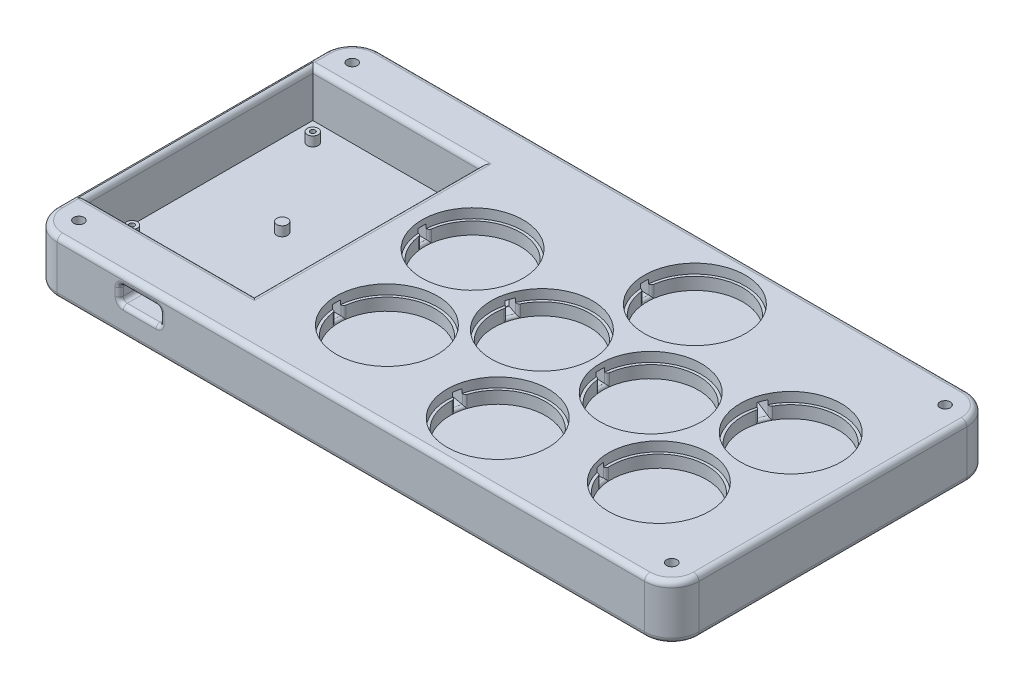
SolidWorks part; units mm, degrees
note: The reader was unsure of these and kept them because the rebuilt part matched: shared geometry of "Sketch1<3>", "Sketch1<5>", "Sketch1<6>".
ref_plane "Front Plane" through (0, 0, 0) normal (0, 0, 1) x (1, 0, 0)
ref_plane "Top Plane" through (0, 0, 0) normal (0, 1, 0) x (1, 0, 0)
ref_plane "Right Plane" through (0, 0, 0) normal (1, 0, 0) x (0, 0, -1)
sketch "Sketch1" plane through (0, 0, 0) normal (0, 1, 0) x (1, 0, 0)
  line L0 (-50.1645, 82.8261) -> (10.8355, 82.8261) construction
  line L1 (-50.1645, 0.3261) -> (10.8355, 0.3261) construction
  line L2 (-50.1645, 0.3261) -> (-50.1645, 82.8261) construction
  line L3 (-50.1645, 82.8261) -> (10.8355, 82.8261) construction
  line L4 (10.8355, 0.3261) -> (10.8355, 82.8261) construction
  line L6 (-50.1645, 82.8261) -> (-50.1645, 0.3261) construction
  line L9 (95.3355, 77.8261) -> (95.3355, 5.3261) construction
  line L10 (95.3355, 41.5761) -> (-73.6645, 41.5761) construction
  line L11 (-53.6645, 100.8261) -> (182.3355, 100.8261)
  line L12 (-50.6645, 97.8261) -> (179.3355, 97.8261)
  line L13 (-50.6645, 97.8261) -> (-50.6645, -14.6739)
  line L14 (-50.6645, -14.6739) -> (179.3355, -14.6739)
  line L15 (179.3355, 97.8261) -> (179.3355, -14.6739)
  line L16 (182.3355, 100.8261) -> (182.3355, -17.6739)
  line L17 (-53.6645, -17.6739) -> (182.3355, -17.6739)
  line L18 (-53.6645, 100.8261) -> (-53.6645, -17.6739)
  line L19 (-50.4645, 83.1261) -> (11.1355, 83.1261)
  line L20 (11.1355, 0.0261) -> (11.1355, 83.1261)
  line L21 (-50.4645, 0.0261) -> (11.1355, 0.0261)
  line L22 (-50.4645, 83.1261) -> (-50.4645, 0.0261)
  circle A0 centre (36.8355, 54.5761) radius 17.6
  circle A1 centre (45.3355, 14.5761) radius 17.6
  circle A2 centre (145.3355, 14.5761) radius 17.6
  circle A4 centre (75.3355, 41.5761) radius 17.6
  circle A5 centre (115.3355, 41.5761) radius 17.6
  circle A6 centre (95.3355, 5.3261) radius 17.6
  circle A7 centre (153.8355, 54.5761) radius 17.6
  circle A8 centre (95.3355, 77.8261) radius 17.6
  point P12 (10.8355, 41.5761)
  point P27 (-50.6645, 41.5761)
  dimension "D3" = 35.2
  dimension "D4" = 26
  dimension "D5" = 40
  dimension "D15" = 112.5
  dimension "D20" = 82.5
  dimension "D1" = 61
  dimension "D2" = 82.5
  dimension "D6" = 20
  dimension "D7" = 72.5
  dimension "D8" = 36.25
  dimension "D9" = 100
  dimension "D10" = 30
  dimension "D11" = 117
  dimension "D12" = 38.5
  dimension "D13" = 40
  dimension "D14" = 27
  dimension "D16" = 230
  dimension "D17" = 3
  dimension "D18" = 0.5
  dimension "D19" = 0.3
extrude "Boss-Extrude1" add sketch "Sketch1" against normal blind 5 contours L15 L12 L13 L14 A8 A7 A6 A5 A4 A2 A1 A0 L6 L0 L4 L1 | L11 L18 L17 L16 L12 L15 L14 L13 | L0 L6 L1 L4 | A0 | A1 | A4 | A8 | A5 | A7 | A2 | A6 | L19 L22 L21 L20
extrude "Boss-Extrude2" add sketch "Sketch1<3>" along normal blind 15 contours L11 L18 L17 L16 L12 L15 L14 L13 | L15 L12 L13 L14 A8 A7 A6 A5 A4 A2 A1 A0 L22 L19 L20 L21
sketch "Sketch1<3>" plane through (0, 0, 0) normal (0, 1, 0) x (1, 0, 0) same geometry as "Sketch1"
extrude "Cut-Extrude2" cut sketch "Sketch1<5>" against normal blind 2 contours L0 L6 L1 L4 | A0 | A1 | A4 | A8 | A5 | A7 | A2 | A6 | L19 L22 L21 L20
sketch "Sketch1<5>" plane through (0, 0, 0) normal (0, 1, 0) x (1, 0, 0) same geometry as "Sketch1"
ref_plane "Plane1" through (0, 12, 0) normal (0, 1, 0) x (1, 0, 0)
sketch "Sketch2" plane through (0, 12, 0) normal (0, 1, 0) x (1, 0, 0)
  line L0 (27.7355, 14.5761) -> (11.1355, 14.5761) construction
  line L1 (19.2355, 54.5761) -> (11.1355, 54.5761) construction
  line L2 (19.2995, 56.0761) -> (11.1355, 56.0761)
  line L3 (27.7995, 16.0761) -> (11.1355, 16.0761)
  line L4 (182.3355, 100.8261) -> (-53.6645, 100.8261)
  line L5 (-53.6645, 100.8261) -> (-53.6645, -17.6739)
  line L6 (-53.6645, -17.6739) -> (182.3355, -17.6739)
  line L7 (182.3355, -17.6739) -> (182.3355, 100.8261)
  line L8 (182.3355, 100.8261) -> (-53.6645, 100.8261)
  line L9 (-53.6645, 100.8261) -> (-53.6645, -17.6739)
  line L10 (-53.6645, -17.6739) -> (182.3355, -17.6739)
  line L11 (182.3355, -17.6739) -> (182.3355, 100.8261)
  line L12 (11.1355, 83.1261) -> (-50.4645, 83.1261)
  line L13 (-50.4645, 83.1261) -> (-50.4645, 0.0261)
  line L14 (-50.4645, 0.0261) -> (11.1355, 0.0261)
  line L15 (11.1355, 0.0261) -> (11.1355, 83.1261)
  line L16 (11.1355, 83.1261) -> (-50.4645, 83.1261)
  line L17 (-50.4645, 83.1261) -> (-50.4645, 0.0261)
  line L18 (-50.4645, 0.0261) -> (11.1355, 0.0261)
  line L19 (11.1355, 0.0261) -> (11.1355, 83.1261)
  line L20 (27.7995, 13.0761) -> (11.1355, 13.0761)
  line L21 (11.1355, 77.8261) -> (77.7355, 77.8261) construction
  line L22 (11.1355, 76.3261) -> (77.7995, 76.3261)
  line L23 (11.1355, 79.3261) -> (77.7995, 79.3261)
  line L24 (58.6605, 47.2066) -> (53.5105, 48.9456) construction
  line L25 (59.201, 48.6073) -> (53.9297, 50.3872)
  line L26 (58.2412, 45.765) -> (52.97, 47.5449)
  line L27 (62.6418, 11.3744) -> (78.0292, 8.5278) construction
  line L28 (62.306, 9.9111) -> (77.8193, 7.0411)
  line L29 (62.8517, 12.861) -> (78.365, 9.9911)
  line L30 (45.0626, 13.1011) -> (95.0626, 3.8511) construction
  line L31 (45.6084, 16.0511) -> (95.6084, 6.8011) construction
  line L32 (112.6418, 8.5278) -> (128.0292, 11.3744) construction
  line L33 (112.8517, 7.0411) -> (128.365, 9.9111)
  line L34 (112.306, 9.9911) -> (127.8193, 12.861)
  line L35 (95.6084, 3.8511) -> (145.6084, 13.1011) construction
  line L36 (95.0626, 6.8011) -> (145.0626, 16.0511) construction
  line L37 (95.3355, 5.3261) -> (145.3355, 14.5761) construction
  line L38 (92.9355, 41.5761) -> (97.7355, 41.5761) construction
  line L39 (92.8715, 40.0761) -> (97.7995, 40.0761)
  line L40 (92.8715, 43.0761) -> (97.7995, 43.0761)
  line L41 (111.6911, 71.3258) -> (137.4799, 61.0764) construction
  line L42 (111.0776, 69.9555) -> (136.9854, 59.6588)
  line L43 (112.1856, 72.7434) -> (138.0934, 62.4467)
  line L44 (94.7815, 76.4321) -> (153.2815, 53.1821) construction
  line L45 (95.3355, 77.8261) -> (153.8355, 54.5761) construction
  line L46 (95.8895, 79.22) -> (154.3895, 55.97) construction
  line L47 (45.3355, 14.5761) -> (95.3355, 5.3261) construction
  line L48 (27.7355, 16.0761) -> (11.1355, 16.0761) construction
  line L49 (27.7355, 13.0761) -> (11.1355, 13.0761) construction
  line L50 (19.2995, 53.0761) -> (11.1355, 53.0761)
  line L51 (25.2691, 56.0761) -> (5.5876, 56.0761) construction
  line L52 (25.2691, 54.5761) -> (5.5876, 54.5761) construction
  line L53 (25.2691, 53.0761) -> (5.5876, 53.0761) construction
  line L54 (11.1355, 79.3261) -> (77.7355, 79.3261) construction
  line L55 (11.1355, 76.3261) -> (77.7355, 76.3261) construction
  line L56 (59.1403, 48.6278) -> (53.9904, 50.3667) construction
  line L57 (58.1806, 45.7855) -> (53.0307, 47.5244) construction
  line L58 (92.9355, 40.0761) -> (97.7355, 40.0761) construction
  line L59 (92.9355, 43.0761) -> (97.7355, 43.0761) construction
  circle A0 centre (145.3355, 14.5761) radius 17.6 construction
  circle A1 centre (153.8355, 54.5761) radius 17.6 construction
  circle A2 centre (95.3355, 77.8261) radius 17.6 construction
  circle A3 centre (95.3355, 5.3261) radius 17.6 construction
  circle A4 centre (115.3355, 41.5761) radius 17.6 construction
  circle A5 centre (75.3355, 41.5761) radius 17.6 construction
  circle A6 centre (45.3355, 14.5761) radius 17.6 construction
  circle A7 centre (36.8355, 54.5761) radius 17.6 construction
  circle A8 centre (145.3355, 14.5761) radius 17.6
  circle A9 centre (153.8355, 54.5761) radius 17.6
  circle A10 centre (95.3355, 77.8261) radius 17.6
  circle A11 centre (95.3355, 5.3261) radius 17.6
  circle A12 centre (115.3355, 41.5761) radius 17.6
  circle A13 centre (75.3355, 41.5761) radius 17.6
  circle A14 centre (45.3355, 14.5761) radius 17.6
  circle A15 centre (36.8355, 54.5761) radius 17.6
  circle A16 centre (45.3355, 14.5761) radius 17.6 construction
  dimension "D3" = 1.5
  dimension "D5" = 66.6
  dimension "D6" = 1.5
  dimension "D8" = 1.5
  dimension "D9" = 1.5
  dimension "D10" = 1.5
  dimension "D18" = 1.5
  dimension "D1" = 0
  dimension "D2" = 0
  dimension "D4" = 1.5
  dimension "D7" = 1.5
  dimension "D11" = 1.5
  dimension "D12" = 1.5
  dimension "D13" = 1.5
  dimension "D14" = 1.5
  dimension "D15" = 1.5
  dimension "D16" = 1.5
  dimension "D17" = 1.5
  dimension "D19" = 1.5
extrude "Cut-Extrude3" cut sketch "Sketch2" against normal blind 4 and the other way blind 1
sketch "Sketch3" plane through (0, 0, 17.6739) normal (0, 0, 1) x (1, 0, 0)
  line L1 (-20.8645, 15) -> (-5.8645, 15)
  line L2 (-20.8645, 15) -> (-20.8645, -2)
  line L3 (-20.8645, -2) -> (-5.8645, -2)
  line L4 (-50.4645, 15) -> (-50.4645, -2)
  line L5 (-50.4645, -2) -> (11.1355, -2)
  line L6 (11.1355, -2) -> (11.1355, 15)
  line L7 (11.1355, 15) -> (-50.4645, 15)
  line L8 (-50.4645, 15) -> (-50.4645, -2)
  line L9 (-50.4645, -2) -> (11.1355, -2)
  line L10 (11.1355, -2) -> (11.1355, 15)
  line L11 (11.1355, 15) -> (-50.4645, 15)
  line L12 (-5.8645, 15) -> (-5.8645, -2)
  line L13 (-20.8645, 11) -> (-5.8645, 11)
  line L14 (-20.8645, 11) -> (-20.8645, 5)
  line L15 (-20.8645, 5) -> (-5.8645, 5)
  line L16 (-5.8645, 11) -> (-5.8645, 5)
  dimension "D2" = 17
  dimension "D3" = 15
  dimension "D4" = 7
  dimension "D5" = 4
  dimension "D1" = 0
extrude "Cut-Extrude4" cut sketch "Sketch3" against normal up to next contours L2 L15 L12 L13
sketch "Sketch4" plane through (0, -2, 0) normal (0, 1, 0) x (1, 0, 0)
  line L0 (-50.4645, 83.1261) -> (11.1355, 83.1261) construction
  line L1 (-50.4645, 83.1261) -> (-50.4645, 0.0261) construction
  line L2 (11.1355, 0.0261) -> (11.1355, 83.1261) construction
  line L3 (-50.4645, 83.1261) -> (11.1355, 83.1261) construction
  line L4 (-50.4645, 0.0261) -> (11.1355, 0.0261) construction
  line L5 (11.1355, 0.0261) -> (11.1355, 83.1261) construction
  circle A0 centre (-43.4645, 76.1261) radius 2
  circle A1 centre (4.1355, 76.1261) radius 2
  circle A2 centre (-46.9645, 13.1261) radius 2
  circle A3 centre (3.1355, 7.0261) radius 2
  circle A4 centre (-20.4645, 41.8761) radius 2
  circle A5 centre (-43.4645, 76.1261) radius 0.925
  circle A6 centre (4.1355, 76.1261) radius 0.925
  circle A7 centre (-46.9645, 13.1261) radius 0.925
  dimension "D1" = 4
  dimension "D2" = 7
  dimension "D3" = 7
  dimension "D4" = 7
  dimension "D5" = 7
  dimension "D6" = 3.5
  dimension "D7" = 70
  dimension "D8" = 7
  dimension "D9" = 8
  dimension "D10" = 30
  dimension "D11" = 41.25
  dimension "D12" = 1.85
extrude "Boss-Extrude3" add sketch "Sketch4" along normal blind 3.5
extrude "Boss-Extrude4" add sketch "Sketch1<6>" along normal blind 7 and the other way blind 2 contours A0 | A4 | A8 | A5 | A6 | A1 | A7 | A2
sketch "Sketch1<6>" plane through (0, 0, 0) normal (0, 1, 0) x (1, 0, 0) same geometry as "Sketch1"
fillet "Fillet1" radius 1 64 edges at (77.7995, 10.5, -79.3261) (77.7355, 13, -77.8261) (77.7995, 10.5, -76.3261) (19.2995, 10.5, -53.0761) (19.2355, 13, -54.5761) (19.2995, 10.5, -56.0761) (58.2412, 10.5, -45.765) (58.6605, 13, -47.2066) (59.201, 10.5, -48.6073) (77.8193, 10.5, -7.0411) (78.0292, 13, -8.5278) (78.365, 10.5, -9.9911) (97.7995, 10.5, -40.0761) (97.7355, 13, -41.5761) (97.7995, 10.5, -43.0761) (128.365, 10.5, -9.9111) (128.0292, 13, -11.3744) (127.8193, 10.5, -12.861) (136.9854, 10.5, -59.6588) (138.0934, 10.5, -62.4467) (137.4799, 13, -61.0764) (112.1856, 10.5, -72.7434) (111.6911, 13, -71.3258) (111.0776, 10.5, -69.9555) (92.8715, 10.5, -40.0761) (92.9355, 13, -41.5761) (92.8715, 10.5, -43.0761) (112.8517, 10.5, -7.0411) (112.6418, 13, -8.5278) (112.306, 10.5, -9.9911) (62.306, 10.5, -9.9111) (62.6418, 13, -11.3744) (62.8517, 10.5, -12.861) (27.7355, 13, -14.5761) (27.7995, 10.5, -13.0761) (27.7995, 10.5, -16.0761) (11.1355, 10.5, -16.0761) (11.1355, 13, -14.5761) (11.1355, 10.5, -13.0761) (53.9297, 10.5, -50.3872) (52.97, 10.5, -47.5449) (53.5105, 13, -48.9456) (11.1355, 10.5, -56.0761) (11.1355, 13, -54.5761) (11.1355, 10.5, -53.0761) (11.1355, 10.5, -76.3261) (11.1355, 13, -77.8261) (11.1355, 8, -77.8261) (11.1355, 10.5, -79.3261) (11.1355, 8, -14.5761) (11.1355, 8, -54.5761) (128.0292, 8, -11.3744) (97.7355, 8, -41.5761) (137.4799, 8, -61.0764) (111.6911, 8, -71.3258) (77.7355, 8, -77.8261) (78.0292, 8, -8.5278) (112.6418, 8, -8.5278) (92.9355, 8, -41.5761) (53.5105, 8, -48.9456) (62.6418, 8, -11.3744) (27.7355, 8, -14.5761) (19.2355, 8, -54.5761) (58.6605, 8, -47.2066)
fillet "Fillet2" radius 1.5 12 edges at (-13.3645, 11, -0.0261) (-13.3645, 5, -0.0261) (-13.3645, 5, 17.6739) (-13.3645, 11, 17.6739) (-5.8645, 11, 8.8239) (-5.8645, 8, 17.6739) (-5.8645, 5, 8.8239) (-5.8645, 8, -0.0261) (-20.8645, 8, -0.0261) (-20.8645, 5, 8.8239) (-20.8645, 8, 17.6739) (-20.8645, 11, 8.8239)
sketch "Sketch7" plane through (0, 15, 0) normal (0, 1, 0) x (1, 0, 0)
  line L0 (-53.6645, -17.6739) -> (182.3355, -17.6739) construction
  line L1 (-53.6645, 100.8261) -> (-53.6645, -17.6739) construction
  line L2 (-53.6645, 41.5761) -> (182.3355, 41.5761) construction
  line L3 (182.3355, 100.8261) -> (182.3355, -17.6739) construction
  line L4 (64.3355, 100.8261) -> (64.3355, -17.6739) construction
  line L5 (-53.6645, 100.8261) -> (182.3355, 100.8261) construction
  circle A0 centre (-44.6645, -8.6739) radius 1.9
  circle A1 centre (-44.6645, 91.8261) radius 1.9
  circle A2 centre (173.3355, -8.6739) radius 1.9
  circle A3 centre (173.3355, 91.8261) radius 1.9
  dimension "D1" = 3.8
  dimension "D2" = 9
  dimension "D3" = 9
extrude "Cut-Extrude5" cut sketch "Sketch7" against normal blind 6
fillet "Fillet3" radius 10 4 edges at (-53.6645, 5, 17.6739) (-53.6645, 5, -100.8261) (182.3355, 5, -100.8261) (182.3355, 5, 17.6739)
fillet "Fillet4" radius 2 20 edges at (-50.7356, -5, 14.745) (-53.6645, -5, -41.5761) (-50.7356, -5, -97.8972) (64.3355, -5, -100.8261) (179.4066, -5, -97.8972) (182.3355, -5, -41.5761) (179.4066, -5, 14.745) (-50.7356, 15, 14.745) (-53.6645, 15, -41.5761) (-50.7356, 15, -97.8972) (64.3355, 15, -100.8261) (179.4066, 15, -97.8972) (182.3355, 15, -41.5761) (179.4066, 15, 14.745) (64.3355, -5, 17.6739) (64.3355, 15, 17.6739) (-50.4645, 15, -41.5761) (-19.6645, 15, -0.0261) (11.1355, 15, -41.5761) (-19.6645, 15, -83.1261)
sketch "Sketch8" plane through (0, 15, 0) normal (0, 1, 0) x (1, 0, 0)
  line L8 (13.1355, -1.9739) -> (-51.6645, -1.9739)
  line L9 (-51.6645, -1.9739) -> (-51.6645, -7.6739)
  line L10 (-43.6645, -15.6739) -> (172.3355, -15.6739)
  line L11 (180.3355, -7.6739) -> (180.3355, 90.8261)
  line L12 (172.3355, 98.8261) -> (-43.6645, 98.8261)
  line L13 (-51.6645, 90.8261) -> (-51.6645, 85.1261)
  line L14 (-51.6645, 85.1261) -> (13.1355, 85.1261)
  line L15 (13.1355, 85.1261) -> (13.1355, -1.9739)
  line L16 (13.1355, -1.9739) -> (-51.6645, -1.9739)
  line L17 (-51.6645, -1.9739) -> (-51.6645, -7.6739)
  line L18 (-43.6645, -15.6739) -> (172.3355, -15.6739)
  line L19 (180.3355, -7.6739) -> (180.3355, 90.8261)
  line L20 (172.3355, 98.8261) -> (-43.6645, 98.8261)
  line L21 (-51.6645, 90.8261) -> (-51.6645, 85.1261)
  line L22 (-51.6645, 85.1261) -> (13.1355, 85.1261)
  line L23 (13.1355, 85.1261) -> (13.1355, -1.9739)
  circle A0 centre (95.3355, 5.3261) radius 17.6 construction
  circle A1 centre (45.3355, 14.5761) radius 17.6
  circle A2 centre (45.3355, 14.5761) radius 17.6 construction
  circle A3 centre (36.8355, 54.5761) radius 17.6
  arc A4 (-51.6645, -7.6739) -> (-43.6645, -15.6739) centre (-43.6645, -7.6739) ccw
  arc A5 (172.3355, -15.6739) -> (180.3355, -7.6739) centre (172.3355, -7.6739) ccw
  arc A6 (180.3355, 90.8261) -> (172.3355, 98.8261) centre (172.3355, 90.8261) ccw
  arc A7 (-43.6645, 98.8261) -> (-51.6645, 90.8261) centre (-43.6645, 90.8261) ccw
  arc A8 (-51.6645, -7.6739) -> (-43.6645, -15.6739) centre (-43.6645, -7.6739) ccw
  arc A9 (172.3355, -15.6739) -> (180.3355, -7.6739) centre (172.3355, -7.6739) ccw
  arc A10 (180.3355, 90.8261) -> (172.3355, 98.8261) centre (172.3355, 90.8261) ccw
  arc A11 (-43.6645, 98.8261) -> (-51.6645, 90.8261) centre (-43.6645, 90.8261) ccw
  circle A12 centre (36.8355, 54.5761) radius 17.6 construction
  circle A13 centre (145.3355, 14.5761) radius 17.6 construction
  circle A14 centre (153.8355, 54.5761) radius 17.6 construction
  circle A15 centre (115.3355, 41.5761) radius 17.6 construction
  circle A16 centre (75.3355, 41.5761) radius 17.6 construction
  circle A17 centre (95.3355, 77.8261) radius 17.6 construction
  circle A18 centre (95.3355, 5.3261) radius 17.6 construction
  circle A19 centre (145.3355, 14.5761) radius 17.6 construction
  circle A20 centre (153.8355, 54.5761) radius 17.6 construction
  circle A21 centre (115.3355, 41.5761) radius 17.6 construction
  circle A22 centre (75.3355, 41.5761) radius 17.6 construction
  circle A23 centre (95.3355, 77.8261) radius 17.6 construction
  circle A24 centre (36.8355, 54.5761) radius 18.6
  circle A25 centre (95.3355, 77.8261) radius 18.6
  circle A26 centre (115.3355, 41.5761) radius 18.6
  circle A27 centre (75.3355, 41.5761) radius 18.6
  circle A28 centre (95.3355, 5.3261) radius 18.6
  circle A29 centre (45.3355, 14.5761) radius 18.6
  circle A30 centre (145.3355, 14.5761) radius 18.6
  circle A31 centre (153.8355, 54.5761) radius 18.6
  circle M31 centre (95.3355, 77.8261) radius 17.6
  circle M32 centre (153.8355, 54.5761) radius 17.6
  circle M33 centre (95.3355, 5.3261) radius 17.6
  circle M34 centre (115.3355, 41.5761) radius 17.6
  circle M35 centre (75.3355, 41.5761) radius 17.6
  circle M36 centre (145.3355, 14.5761) radius 17.6
  circle M37 centre (45.3355, 14.5761) radius 17.6
  circle M38 centre (36.8355, 54.5761) radius 17.6
  dimension "D4" = 1
  dimension "D1" = 0
  dimension "D2" = 0
  dimension "D3" = 0
extrude "Cut-Extrude6" cut sketch "Sketch8" against normal blind 3.5 contours A24 M38 | A27 M35 | A28 M33 | A30 M36 | A29 M37 | A26 M34 | A31 M32 | A25 M31
